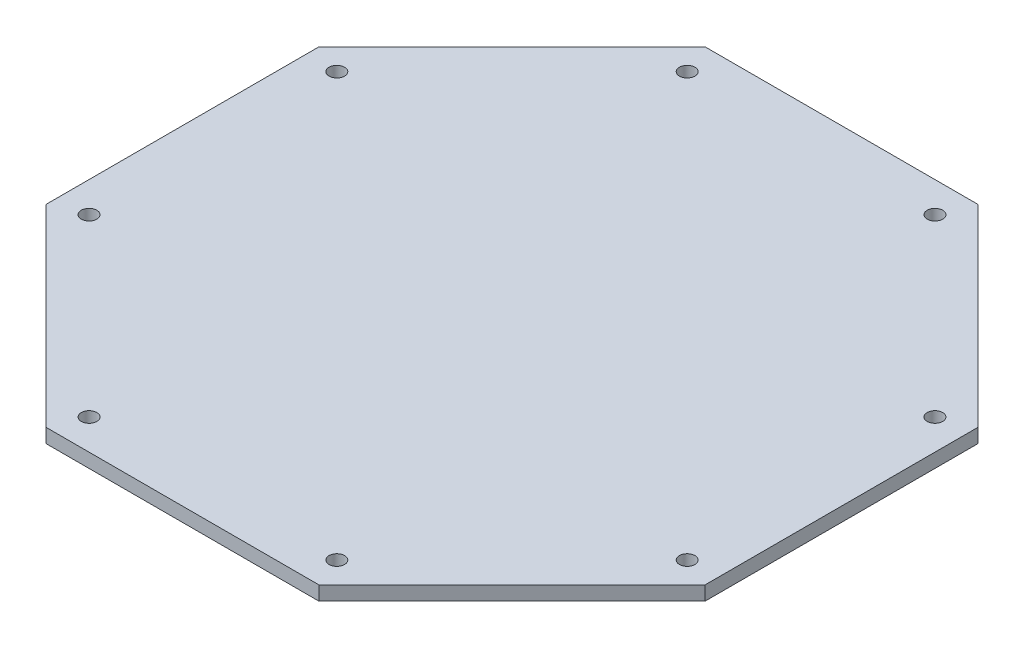
SolidWorks part; units mm, degrees
ref_plane "Plano frontal" through (0, 0, 0) normal (0, 0, 1) x (1, 0, 0)
ref_plane "Plano superior" through (0, 0, 0) normal (0, 1, 0) x (1, 0, 0)
ref_plane "Plano direito" through (0, 0, 0) normal (1, 0, 0) x (0, 0, -1)
sketch "Esboço1" plane through (0, 0, 0) normal (0, 1, 0) x (1, 0, 0)
  line L1 (70, 28.9949) -> (28.9949, 70)
  line L2 (28.9949, 70) -> (-28.9949, 70)
  line L3 (-28.9949, 70) -> (-70, 28.9949)
  line L4 (-70, 28.9949) -> (-70, -28.9949)
  line L5 (-70, -28.9949) -> (-28.9949, -70)
  line L6 (-28.9949, -70) -> (28.9949, -70)
  line L7 (28.9949, -70) -> (70, -28.9949)
  line L8 (70, -28.9949) -> (70, 28.9949)
  circle A0 centre (0, 0) radius 70 construction
  point P13 (70, 0)
  dimension "D1" = 140
extrude "Ressalto-extrusão1" add sketch "Esboço1" along normal mid plane 3
sketch "Esboço2" plane through (0, -1.5, 0) normal (0, -1, 0) x (1, 0, 0)
  line L0 (-28.9949, 70) -> (-26.3162, 63.5328) construction
  line L1 (-28.9949, 70) -> (28.9949, 70) construction
  line L2 (26.3162, 63.5328) -> (28.9949, 70) construction
  line L3 (63.5328, 26.3162) -> (70, 28.9949) construction
  line L4 (63.5328, -26.3162) -> (70, -28.9949) construction
  line L5 (70, 28.9949) -> (70, -28.9949) construction
  line L6 (26.3162, -63.5328) -> (28.9949, -70) construction
  line L7 (-28.9949, -70) -> (-26.3162, -63.5328) construction
  line L8 (-70, 28.9949) -> (-63.5328, 26.3162) construction
  line L9 (-70, -28.9949) -> (-63.5328, -26.3162) construction
  line L10 (28.9949, 70) -> (70, 28.9949) construction
  line L11 (70, -28.9949) -> (28.9949, -70) construction
  line L12 (28.9949, -70) -> (-28.9949, -70) construction
  line L13 (-70, -28.9949) -> (-70, 28.9949) construction
  line L14 (-28.9949, -70) -> (-70, -28.9949) construction
  circle A0 centre (-26.3162, 63.5328) radius 1.65
  circle A1 centre (26.3162, 63.5328) radius 1.65
  circle A2 centre (63.5328, 26.3162) radius 1.65
  circle A3 centre (63.5328, -26.3162) radius 1.65
  circle A4 centre (26.3162, -63.5328) radius 1.65
  circle A5 centre (-26.3162, -63.5328) radius 1.65
  circle A6 centre (-63.5328, 26.3162) radius 1.65
  circle A7 centre (-63.5328, -26.3162) radius 1.65
  point P45 (63.5328, -25.8343)
  point P46 (0, 0)
  point P47 (0, 0)
  dimension "D3" = 3.3
  dimension "D1" = 67.5
  dimension "D2" = 7
  dimension "D4" = 67.5
  dimension "D5" = 67.5
  dimension "D6" = 67.5
  dimension "D7" = 67.5
  dimension "D8" = 67.5
  dimension "D9" = 67.5
  dimension "D10" = 67.5
extrude "Corte-extrusão1" cut sketch "Esboço2" against normal through all
